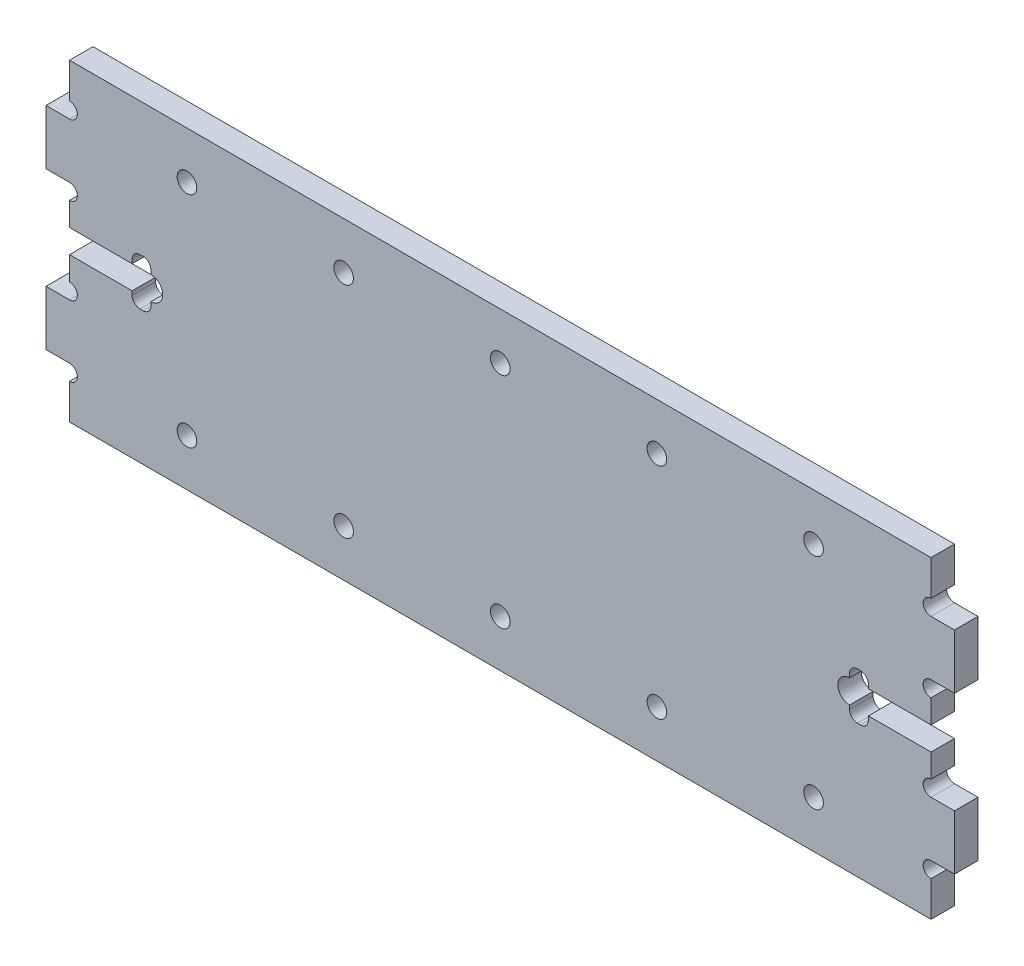
SolidWorks part; units mm, degrees
material "Acrylic (Medium-high impact)"
ref_plane "Front Plane" through (0, 0, 0) normal (0, 0, 1) x (1, 0, 0)
ref_plane "Top Plane" through (0, 0, 0) normal (0, 1, 0) x (1, 0, 0)
ref_plane "Right Plane" through (0, 0, 0) normal (1, 0, 0) x (0, 0, -1)
sketch "Sketch1" plane through (0, 0, 0) normal (0, 0, 1) x (1, 0, 0)
  line L0 (0, 20) -> (0, -20) construction
  line L1 (-55, 20) -> (55, 20)
  line L2 (-55, 20) -> (-55, -20)
  line L3 (-55, -20) -> (55, -20)
  line L4 (55, 20) -> (55, -20)
  line L5 (55, 0) -> (-55, 0) construction
  point P8 (0, 0)
extrude "Boss-Extrude1" add sketch "Sketch1" along normal blind 3
sketch "Sketch2" plane through (0, 0, 3) normal (0, 0, 1) x (1, 0, 0)
  line L0 (-55, 0) -> (55, 0) construction
  line L1 (-55, 20) -> (-55, -20) construction
  line L2 (55, -20) -> (55, 20) construction
  line L3 (55, 0) -> (55, -20) construction
  line L4 (55, 0) -> (55, 20) construction
  line L5 (55, 20) -> (58, 20) construction
  line L6 (58, 20) -> (58, -20) construction
  line L7 (58, -20) -> (55, -20) construction
  line L8 (0, 20) -> (0, -20) construction
  line L9 (55, 20) -> (-55, 20) construction
  line L10 (-55, -20) -> (55, -20) construction
  line L11 (55, -10) -> (58, -10) construction
  line L12 (55, 10) -> (58, 10) construction
  line L13 (58, 10) -> (58, 13.5)
  line L14 (58, 10) -> (58, 6.5)
  line L15 (58, 6.5) -> (55, 6.5)
  line L16 (55, 6.5) -> (55, 13.5)
  line L17 (55, 13.5) -> (58, 13.5)
  line L18 (55, -10) -> (55, -6.5)
  line L19 (55, -6.5) -> (58, -6.5)
  line L20 (58, -6.5) -> (58, -13.5)
  line L21 (58, -13.5) -> (55, -13.5)
  line L22 (55, -13.5) -> (55, -10)
  line L23 (-55, 6.5) -> (-55, 13.5)
  line L24 (-55, -13.5) -> (-55, -10)
  line L25 (-55, -10) -> (-55, -6.5)
  line L26 (-55, 10) -> (-58, 10) construction
  line L27 (-55, -10) -> (-58, -10) construction
  line L28 (-58, -20) -> (-55, -20) construction
  line L29 (-58, 20) -> (-58, -20) construction
  line L30 (-55, 20) -> (-58, 20) construction
  line L31 (-58, -13.5) -> (-55, -13.5)
  line L32 (-58, -6.5) -> (-58, -13.5)
  line L33 (-55, -6.5) -> (-58, -6.5)
  line L34 (-55, 13.5) -> (-58, 13.5)
  line L35 (-58, 6.5) -> (-55, 6.5)
  line L36 (-58, 10) -> (-58, 6.5)
  line L37 (-58, 10) -> (-58, 13.5)
extrude "Boss-Extrude2" add sketch "Sketch2" against normal blind 3
sketch "Sketch3" plane through (0, 0, 3) normal (0, 0, 1) x (1, 0, 0)
  line L0 (-55, 0) -> (55, 0) construction
  line L1 (-55, 6.5) -> (-55, -6.5) construction
  line L2 (55, -6.5) -> (55, 6.5) construction
  line L3 (-55, 13.5) -> (-55, 14.5) construction
  line L4 (-55, 20) -> (-55, 13.5) construction
  line L5 (-55, 14.5) -> (55, 14.5) construction
  line L6 (55, 13.5) -> (55, 20) construction
  line L7 (55, 14.5) -> (55, 5.5) construction
  line L8 (55, 5.5) -> (-55, 5.5) construction
  line L9 (-55, -6.5) -> (-55, -5.5) construction
  line L10 (-55, -5.5) -> (55, -5.5) construction
  line L11 (55, -5.5) -> (55, -14.5) construction
  line L12 (55, -20) -> (55, -13.5) construction
  line L13 (55, -14.5) -> (-55, -14.5) construction
  line L14 (-55, -13.5) -> (-55, -20) construction
  circle A1 centre (-55, 14.5) radius 1
  circle A2 centre (-55, 5.5) radius 1
  circle A3 centre (-55, -5.5) radius 1
  circle A4 centre (-55, -14.5) radius 1
  circle A5 centre (55, 14.5) radius 1
  circle A6 centre (55, 5.5) radius 1
  circle A7 centre (55, -5.5) radius 1
  circle A8 centre (55, -14.5) radius 1
  line M2 (-55, 20) -> (-55, 13.5)
  line M6 (-55, 6.5) -> (-55, -6.5)
  line M10 (-55, -13.5) -> (-55, -20)
  line M12 (55, -20) -> (55, -13.5)
  line M16 (55, -6.5) -> (55, 6.5)
  line M20 (55, 13.5) -> (55, 20)
extrude "Cut-Extrude1" cut sketch "Sketch3" against normal blind 3 contours A4 M10 | A3 M6 | A2 M6 | A1 M2 | A7 M16 | A8 M12 | A6 M16 | A5 M20 region at (-54.5756, 14.5, 3) region at (-54.5756, 5.5, 3) region at (-54.5756, -5.5, 3) region at (-54.5756, -14.5, 3) region at (54.5756, 14.5, 3) region at (54.5756, -5.5, 3) region at (54.5756, 5.5, 3) region at (54.5756, -14.5, 3)
sketch "Sketch4" plane through (0, 0, 3) normal (0, 0, 1) x (1, 0, 0)
  line L0 (-55, 0) -> (55, 0) construction
  line L1 (-55, 4.5) -> (-55, -4.5) construction
  line L2 (55, -4.5) -> (55, 4.5) construction
  line L3 (55, 0) -> (55, -1.5) construction
  line L4 (55, -1.5) -> (-55, -1.5) construction
  line L5 (-55, -1.5) -> (-55, 1.5) construction
  line L6 (-55, 1.5) -> (55, 1.5) construction
  line L7 (55, 1.5) -> (47, 1.5) construction
  line L8 (47, 20) -> (47, -20) construction
  line L9 (55, 20) -> (-55, 20) construction
  line L10 (-55, -20) -> (55, -20) construction
  line L11 (-55, 1.5) -> (-47, 1.5) construction
  line L12 (-47, 20) -> (-47, -20) construction
  line L13 (-47, 20) -> (-44.6, 20) construction
  line L14 (-44.6, 20) -> (-44.6, -20) construction
  line L15 (47, 20) -> (44.6, 20) construction
  line L16 (44.6, 20) -> (44.6, -20) construction
  line L17 (55, 1.5) -> (55, 3) construction
  line L18 (55, 3) -> (-55, 3) construction
  line L19 (-55, 3) -> (-55, -3) construction
  line L20 (-55, -3) -> (55, -3) construction
  line L21 (-44.6, 0) -> (-43.1, 0) construction
  line L22 (44.6, 0) -> (43.1, 0) construction
  line L24 (-55, 1.5) -> (-47, 1.5)
  line L25 (-55, 1.5) -> (-55, -1.5)
  line L26 (-55, -1.5) -> (-47, -1.5)
  line L27 (-47, 1.5) -> (-47, -1.5)
  line L28 (-47, 3) -> (-44.6, 3)
  line L29 (-47, 3) -> (-47, -3)
  line L30 (-47, -3) -> (-44.6, -3)
  line L31 (-44.6, 3) -> (-44.6, -3)
  line L32 (44.6, 3) -> (47, 3)
  line L33 (44.6, 3) -> (44.6, -3)
  line L34 (44.6, -3) -> (47, -3)
  line L35 (47, 3) -> (47, -3)
  line L36 (47, 1.5) -> (55, 1.5)
  line L37 (47, 1.5) -> (47, -1.5)
  line L38 (47, -1.5) -> (55, -1.5)
  line L39 (55, 1.5) -> (55, -1.5)
  arc A0 (44.6, 1.5) -> (44.6, -1.5) centre (44.6, 0) ccw
  arc A1 (-44.6, 1.5) -> (-44.6, -1.5) centre (-44.6, 0) cw
  line M10 (-55, 4.5) -> (-55, -4.5)
  line M24 (55, -4.5) -> (55, 4.5)
extrude "Cut-Extrude2" cut sketch "Sketch4" against normal blind 3 contours L27 L24 L26 M10 | L31 L28 L29 L27 L30 | A1 L31 | L35 L32 L33 L34 | L33 A0 | L35 L38 L36 M24 region at (-51, 0, 3) region at (-45.8, 0, 3) region at (-43.9634, 0, 3) region at (45.8, 0, 3) region at (43.9634, 0, 3) region at (51, 0, 3)
fillet "Fillet6" radius 1 8 edges at (-44.6, 3, 1.5) (-47, 3, 1.5) (-44.6, -3, 1.5) (-47, -3, 1.5) (47, 3, 1.5) (44.6, 3, 1.5) (47, -3, 1.5) (44.6, -3, 1.5)
sketch "Sketch5" plane through (0, 0, 3) normal (0, 0, 1) x (1, 0, 0)
  line L0 (-55, -1.5) -> (-55, 1.5) construction
  line L1 (55, -1.5) -> (55, 1.5) construction
  line L2 (-55, 0) -> (0, 0) construction
  line L3 (0, 0) -> (55, 0) construction
  line L4 (-27.5, 0) -> (-27.5, 1.5) construction
  line L5 (-27.5, 1.5) -> (-23.5, 1.5) construction
  line L6 (-23.5, 1.5) -> (-23.5, -1.5) construction
  line L7 (-23.5, -1.5) -> (-31.5, -1.5) construction
  line L8 (-31.5, -1.5) -> (-31.5, 1.5) construction
  line L9 (-31.5, 1.5) -> (-27.5, 1.5) construction
  line L10 (27.5, 0) -> (27.5, 1.5) construction
  line L11 (27.5, 1.5) -> (31.5, 1.5) construction
  line L12 (31.5, 1.5) -> (31.5, -1.5) construction
  line L13 (31.5, -1.5) -> (23.5, -1.5) construction
  line L14 (23.5, -1.5) -> (23.5, 1.5) construction
  line L15 (23.5, 1.5) -> (27.5, 1.5) construction
sketch "Sketch6" plane through (0, 0, 3) normal (0, 0, 1) x (1, 0, 0)
  line L0 (0, 0) -> (0, 20) construction
  line L1 (55, 20) -> (-55, 20) construction
  line L2 (0, 20) -> (0, 14) construction
  line L3 (0, 0) -> (0, -20) construction
  line L4 (-55, -20) -> (55, -20) construction
  line L5 (0, -20) -> (0, -14) construction
  circle A0 centre (0, 14) radius 1.25
  circle A1 centre (0, -14) radius 1.25
  circle A2 centre (20, -14) radius 1.25
  circle A3 centre (20, 14) radius 1.25
  circle A4 centre (40, -14) radius 1.25
  circle A5 centre (40, 14) radius 1.25
  circle A6 centre (-20, -14) radius 1.25
  circle A7 centre (-20, 14) radius 1.25
  circle A8 centre (-40, -14) radius 1.25
  circle A9 centre (-40, 14) radius 1.25
  dimension "D1" = 3
  dimension "D2" = 3
extrude "Cut-Extrude4" cut sketch "Sketch6" against normal through all contours A8 | A6 | A1 | A2 | A4 | A5 | A3 | A0 | A7 | A9 region at (0, 14, 3) region at (0, -14, 3) region at (20, -14, 3) region at (20, 14, 3) region at (40, -14, 3) region at (40, 14, 3) region at (-20, -14, 3) region at (-20, 14, 3) region at (-40, -14, 3) region at (-40, 14, 3)
